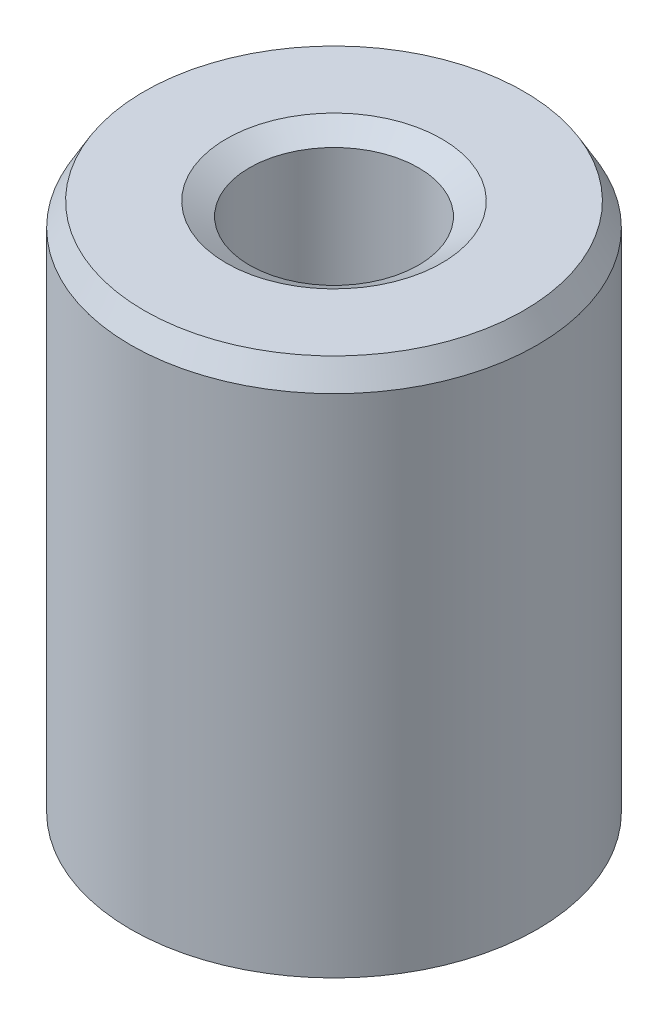
SolidWorks part; units mm, degrees
ref_plane "Front Plane" through (0, 0, 0) normal (0, 0, 1) x (1, 0, 0)
ref_plane "Top Plane" through (0, 0, 0) normal (0, 1, 0) x (1, 0, 0)
ref_plane "Right Plane" through (0, 0, 0) normal (1, 0, 0) x (0, 0, -1)
sketch "Sketch1" plane through (0, 0, 0) normal (0, 1, 0) x (1, 0, 0)
  circle A0 centre (0, 0) radius 5
  dimension "SLEEVE_OD" = 10
extrude "Boss-Extrude1" add sketch "Sketch1" along normal blind 13.3514
sketch "Sketch2" plane through (0, 0, 0) normal (0, 1, 0) x (1, 0, 0)
  circle A0 centre (0, 0) radius 2.0789
  dimension "BORE_D" = 4.1578
extrude "Cut-Extrude1" cut sketch "Sketch2" along normal through all
chamfer "Chamfer1" distance 0.5712 angle 30 4 edges at (0, 13.3514, 2.0789) (0, 0, 2.0789) (0, 0, 5) (0, 13.3514, 5) first distance on face at (0, 13.3514, 2.0789) first distance on face at (0, 0, 2.0789) first distance on face at (0, 13.3514, 5)
